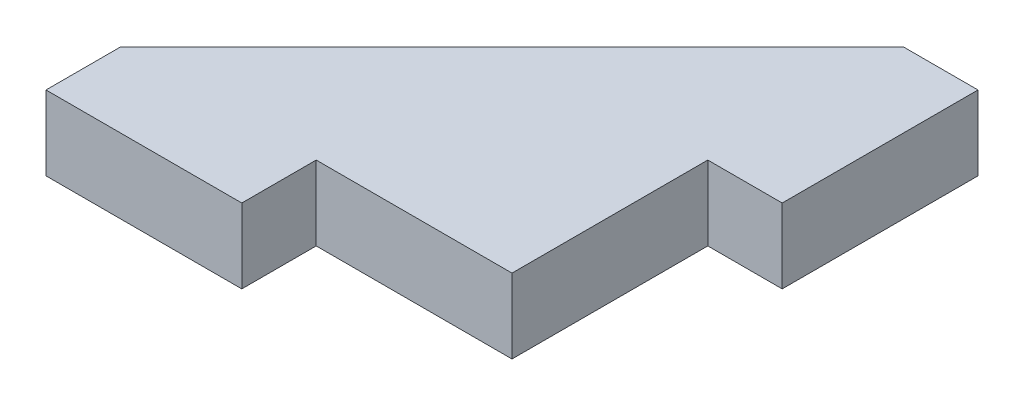
SolidWorks part; units mm, degrees
ref_plane "Front Plane" through (0, 0, 0) normal (0, 0, 1) x (1, 0, 0)
ref_plane "Top Plane" through (0, 0, 0) normal (0, 1, 0) x (1, 0, 0)
ref_plane "Right Plane" through (0, 0, 0) normal (1, 0, 0) x (0, 0, -1)
sketch "Sketch1" plane through (0, 0, 0) normal (0, 1, 0) x (1, 0, 0)
  line L0 (-21.062, -13.6221) -> (4.338, 11.7779)
  line L2 (4.338, 11.7779) -> (9.164, 11.7779)
  line L3 (-21.062, -13.6221) -> (4.338, -13.6221)
  line L4 (4.338, 11.7779) -> (4.338, -13.6221)
  line L5 (4.338, 11.7779) -> (4.338, -0.9221)
  line L6 (4.338, -0.9221) -> (9.164, -0.9221)
  line L7 (9.164, 11.7779) -> (9.164, -0.9221)
  line L8 (-21.062, -13.6221) -> (-8.362, -13.6221)
  line L9 (-21.062, -13.6221) -> (-21.062, -18.4481)
  line L10 (-21.062, -18.4481) -> (-8.362, -18.4481)
  line L11 (-8.362, -13.6221) -> (-8.362, -18.4481)
  dimension "D2" = 25.4
  dimension "D3" = 12.7
  dimension "D4" = 4.826
  dimension "D5" = 4.826
extrude "Boss-Extrude1" add sketch "Sketch1" along normal blind 4.826 contours L11 L3 L9 L10 | L4 L0 L3 | L7 L2 L4 L6 region at (-4.1287, 0, 5.1554) region at (-14.712, 0, 16.0351) region at (6.751, 0, -5.4279)
equation "\"MDF\"= 0.19in"
equation "\"Foamcore\"= .13in"
equation "\"Gmaterial\"= \"MDF\""
equation "\"D4@Sketch1\"=\"MDF\""
equation "\"D5@Sketch1\"=\"MDF\""
equation "\"D1@Boss-Extrude1\"=\"MDF\""
equation "\"PVCID\" = 2.067in"
equation "\"PVCOD\" = 2.375in"
equation "\"GenDiameter\"= 60mm"
equation "\"GenCutDiameter\" = 1.8in"
equation "\"GenCutDistance\" = 1"
equation "\"TowerHeight\" = 6in"
equation "\"TowerFrontBase\" = 3in"
equation "\"FunnelHeight\" = 1in"
equation "\"FunnelAngle\" = 20"
equation "\"TowerSideBase\" = 3in"
equation "\"TowerPanelLength\" = 2in"
equation "\"TowerPanelLeeway\" = 0.5in"
equation "\"BaseLength\" = 9in"
equation "\"BaseWidth\" = 10in"
equation "\"WheelHoleLength\" = 3.25in"
equation "\"WheelHoleWidth\" = 26mm"
equation "\"WheelHoleFromBack\" = 1.5in"
equation "\"DropLength\" = 1in"
equation "\"DropWidth\" = 8.5in"
equation "\"BumperWidth\" = 2in"
equation "\"HoleDiameter\"= 0.25in"
equation "\"SmallHexDiameter\" = 0.185in"
equation "\"SmallHexHeight\" = 0.701in"
equation "\"ScrewSize\" = 0.106in"
equation "\"BigHexDiameter\" = 0.251in"
equation "\"BigHexHeight\" = 0.374in"
equation "\"PCBThickness\" = 0.066in"
equation "\"ConnectorHeight\" = 0.517in"
equation "\"BoardHeight\" = 0.583in"
equation "\"UnoStackHeight\" = 1.351in"
equation "\"UnoStackWidth\" = 3.053in"
equation "\"UnoStackLength\" = 3.152in"
equation "\"HBridgeWidth\" = 1.797in"
equation "\"HBridgeLength\" = 2.236in"
equation "\"DSWidth\" = 1.820in"
equation "\"DSLength\" = 1.833in"
equation "\"StepperWidth\" = 1.799in"
equation "\"StepperLength\" = 2.248in"
equation "\"ULNWidth\" = 1.304in"
equation "\"ULNLength\" = 1.545in"
equation "\"VSwitchHeight\" = 0.392in"
equation "\"VSwitchWidth\" = 0.637in"
equation "\"VSwitchLength\" = 1.097in"
equation "\"SkateWheelDiameter\" = 80mm"
equation "\"SkateWheelThickness\" = 24mm"
equation "\"BaseDistance\" = 3in"
